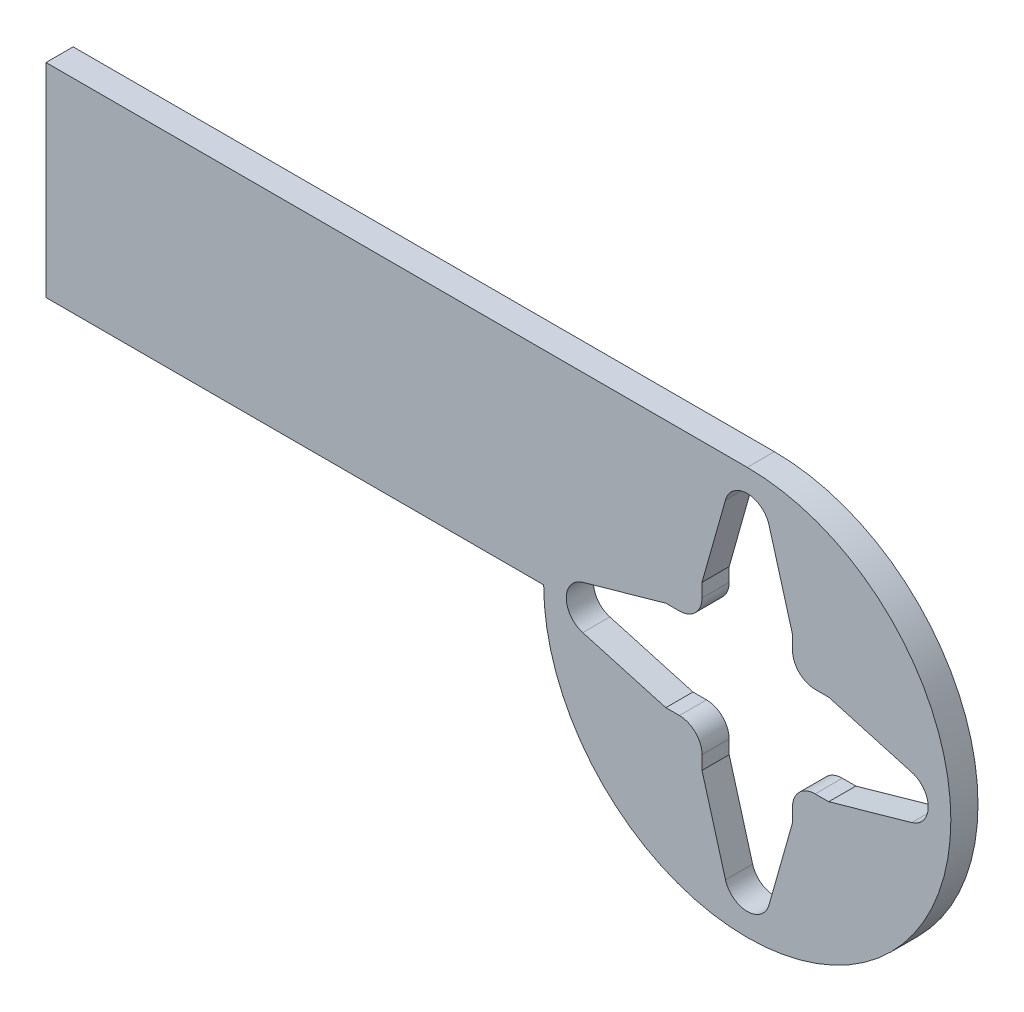
SolidWorks part; units mm, degrees
ref_plane "Front Plane" through (0, 0, 0) normal (0, 0, 1) x (1, 0, 0)
ref_plane "Top Plane" through (0, 0, 0) normal (0, 1, 0) x (1, 0, 0)
ref_plane "Right Plane" through (0, 0, 0) normal (1, 0, 0) x (0, 0, -1)
sketch "Sketch1" plane through (0, 0, 0) normal (0, 0, 1) x (1, 0, 0)
  line L0 (-5, 5) -> (-5, 9)
  line L8 (5, -5) -> (-5, -5)
  line L9 (5, -5) -> (5, 5)
  line L10 (5, 5) -> (-5, 5)
  line L11 (-5, -5) -> (-5, 5)
  line L12 (5, -5) -> (-5, 5) construction
  line L13 (5, 5) -> (-5, -5) construction
  line L14 (-5, 9) -> (-2.4058, 18.1799)
  line L15 (0, -55) -> (0, 55) construction
  line L16 (9, 5) -> (18.1799, 2.4058)
  line L17 (5, 5) -> (5, 9)
  line L18 (55, 0) -> (-55, 0) construction
  line L19 (5, -5) -> (5, -9)
  line L20 (-5, -9) -> (-2.4058, -18.1799)
  line L21 (5, -9) -> (2.4058, -18.1799)
  line L22 (-5, -5) -> (-5, -9)
  line L23 (5, -5) -> (9, -5)
  line L24 (9, -5) -> (18.1799, -2.4058)
  line L25 (-9, -5) -> (-18.1799, -2.4058)
  line L26 (5, 5) -> (9, 5)
  line L27 (-5, -5) -> (-9, -5)
  line L28 (-9, 5) -> (-18.1799, 2.4058)
  line L29 (5, 9) -> (2.4058, 18.1799)
  line L30 (-5, 5) -> (-9, 5)
  line L31 (0, 22.5) -> (-22.5, 0)
  line L32 (-22.5, 0) -> (-22.5, 22.5)
  line L33 (-22.5, 22.5) -> (0, 22.5)
  line L35 (-22.5, 22.5) -> (-77.5, 22.5)
  line L36 (-22.5, 22.5) -> (-22.5, 0)
  line L37 (-22.5, 0) -> (-77.5, 0)
  line L38 (-77.5, 22.5) -> (-77.5, 0)
  circle A0 centre (0, 0) radius 22.5
  circle A1 centre (0, 17.5) radius 2.5
  circle A2 centre (0, -17.5) radius 2.5
  circle A3 centre (17.5, 0) radius 2.5
  circle A4 centre (-17.5, 0) radius 2.5
  circle A5 centre (-7.5, 7.5) radius 2.5
  circle A6 centre (-7.5, -7.5) radius 2.5
  circle A7 centre (7.5, 7.5) radius 2.5
  circle A8 centre (7.5, -7.5) radius 2.5
  arc A9 (-24.8747, 0) -> (-22.3872, -2.25) centre (-24.8747, -2.5) cw
  dimension "D1" = 45
  dimension "D3" = 5
  dimension "D5" = 12.5
  dimension "D6" = 5
  dimension "D9" = 5
  dimension "D11" = 2.5
  dimension "D2" = 10
  dimension "D4" = 4
  dimension "D7" = 4
  dimension "D8" = 12.5
  dimension "D10" = 55
extrude "Boss-Extrude1" add sketch "Sketch1" along normal blind 3 contours A0 A4 L30 L0 A1 L17 L26 A3 L23 L19 A2 L22 L27 | A5 | A7 | A8 | A6 | L33 L31 L32 | L36 L35 L38 L37 region at (15.4599, 15.4599, 0)
sketch "Sketch3" plane through (0, 0, 3) normal (0, 0, 1) x (1, 0, 0)
  line L16 (7.5, -5) -> (9, -5)
  line L17 (5, -9) -> (5, -7.5)
  line L18 (2.4058, -18.1799) -> (5, -9)
  line L19 (-5, -9) -> (-2.4058, -18.1799)
  line L20 (-5, -7.5) -> (-5, -9)
  line L21 (-9, -5) -> (-7.5, -5)
  line L22 (-18.1799, -2.4058) -> (-9, -5)
  line L23 (-9, 5) -> (-18.1799, 2.4058)
  line L24 (-7.5, 5) -> (-9, 5)
  line L25 (-5, 9) -> (-5, 7.5)
  line L26 (-2.4058, 18.1799) -> (-5, 9)
  line L27 (5, 9) -> (2.4058, 18.1799)
  line L28 (5, 7.5) -> (5, 9)
  line L29 (9, 5) -> (7.5, 5)
  line L30 (18.1799, 2.4058) -> (9, 5)
  line L31 (9, -5) -> (18.1799, -2.4058)
  line L32 (7.5, -5) -> (9, -5)
  line L33 (5, -9) -> (5, -7.5)
  line L34 (2.4058, -18.1799) -> (5, -9)
  line L35 (-5, -9) -> (-2.4058, -18.1799)
  line L36 (-5, -7.5) -> (-5, -9)
  line L37 (-9, -5) -> (-7.5, -5)
  line L38 (-18.1799, -2.4058) -> (-9, -5)
  line L39 (-9, 5) -> (-18.1799, 2.4058)
  line L40 (-7.5, 5) -> (-9, 5)
  line L41 (-5, 9) -> (-5, 7.5)
  line L42 (-2.4058, 18.1799) -> (-5, 9)
  line L43 (5, 9) -> (2.4058, 18.1799)
  line L44 (5, 7.5) -> (5, 9)
  line L45 (9, 5) -> (7.5, 5)
  line L46 (18.1799, 2.4058) -> (9, 5)
  line L47 (9, -5) -> (18.1799, -2.4058)
  arc A8 (7.5, -5) -> (5, -7.5) centre (7.5, -7.5) ccw
  arc A9 (-2.4058, -18.1799) -> (2.4058, -18.1799) centre (0, -17.5) ccw
  arc A10 (-5, -7.5) -> (-7.5, -5) centre (-7.5, -7.5) ccw
  arc A11 (-18.1799, 2.4058) -> (-18.1799, -2.4058) centre (-17.5, 0) ccw
  arc A12 (-7.5, 5) -> (-5, 7.5) centre (-7.5, 7.5) ccw
  arc A13 (2.4058, 18.1799) -> (-2.4058, 18.1799) centre (0, 17.5) ccw
  arc A14 (5, 7.5) -> (7.5, 5) centre (7.5, 7.5) ccw
  arc A15 (18.1799, -2.4058) -> (18.1799, 2.4058) centre (17.5, 0) ccw
  arc A16 (7.5, -5) -> (5, -7.5) centre (7.5, -7.5) ccw
  arc A17 (-2.4058, -18.1799) -> (2.4058, -18.1799) centre (0, -17.5) ccw
  arc A18 (-5, -7.5) -> (-7.5, -5) centre (-7.5, -7.5) ccw
  arc A19 (-18.1799, 2.4058) -> (-18.1799, -2.4058) centre (-17.5, 0) ccw
  arc A20 (-7.5, 5) -> (-5, 7.5) centre (-7.5, 7.5) ccw
  arc A21 (2.4058, 18.1799) -> (-2.4058, 18.1799) centre (0, 17.5) ccw
  arc A22 (5, 7.5) -> (7.5, 5) centre (7.5, 7.5) ccw
  arc A23 (18.1799, -2.4058) -> (18.1799, 2.4058) centre (17.5, 0) ccw
  dimension "D1" = 0
